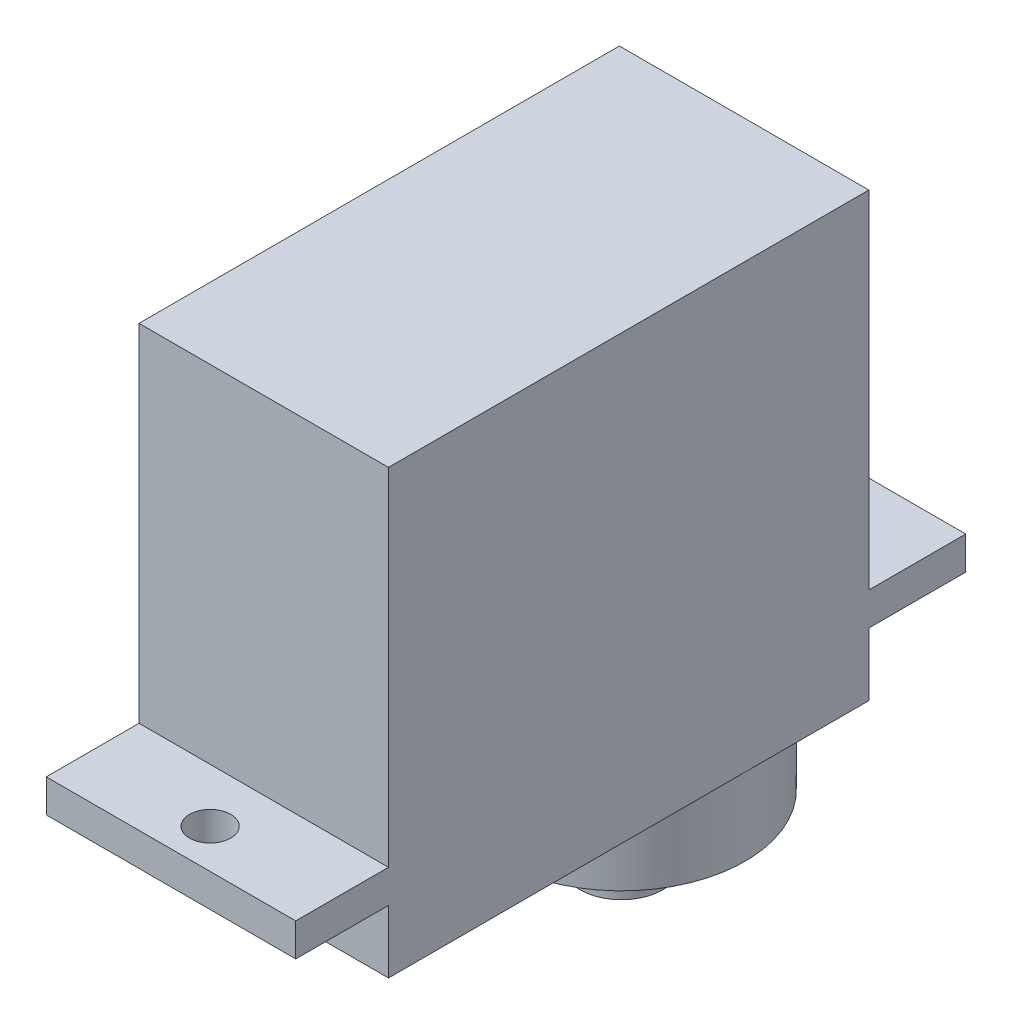
SolidWorks part; units mm, degrees
note: The reader was unsure of these and kept them because the rebuilt part matched: shared geometry of "草图4<2>", "草图6<6>", "草图6<7>".
ref_plane "前视基准面" through (0, 0, 0) normal (0, 0, 1) x (1, 0, 0)
ref_plane "上视基准面" through (0, 0, 0) normal (0, 1, 0) x (1, 0, 0)
ref_plane "右视基准面" through (0, 0, 0) normal (1, 0, 0) x (0, 0, -1)
other "Configuration Table"
other "图形1"
other "图形 (闭合) -1"
sketch "草图3" plane through (0, 0, 0) normal (1, 0, 0) x (0, 0, -1)
  line L1 (-16.8485, -8.5159) -> (15.6515, -8.5159)
  line L2 (-16.8485, -8.5159) -> (-16.8485, 12.9341)
  line L3 (-16.8485, 12.9341) -> (15.6515, 12.9341)
  line L4 (15.6515, -8.5159) -> (15.6515, 12.9341)
  dimension "D1" = 32.5
  dimension "D2" = 21.45
  dimension "D3" = 15.6515
  dimension "D4" = 12.9341
extrude "凸台-拉伸1" add sketch "草图3" along normal mid plane 12.1
sketch "草图4" plane through (0, 0, 0) normal (0, 1, 0) x (1, 0, 0)
  line L0 (0, 0) -> (15.913, 0) construction
  line L1 (-6.05, 10.9515) -> (6.05, 10.9515)
  line L2 (-6.05, 10.9515) -> (-6.05, 15.6516)
  line L3 (-6.05, 15.6516) -> (6.05, 15.6516)
  line L4 (6.05, 10.9515) -> (6.05, 15.6516)
  line L6 (-6.05, -16.9484) -> (6.05, -16.9484)
  line L7 (-6.05, -16.9484) -> (-6.05, -12.3484)
  line L8 (-6.05, -12.3484) -> (6.05, -12.3484)
  line L9 (6.05, -16.9484) -> (6.05, -12.3484)
  dimension "D1" = 12.1
  dimension "D2" = 4.7
  dimension "D3" = 10.9515
  dimension "D4" = 6.05
  dimension "D5" = 4.6
  dimension "D6" = 12.1
  dimension "D7" = 6.05
  dimension "D8" = 12.3484
extrude "切除-拉伸1" cut sketch "草图4" along normal through all from offset 3.8658 offset against normal yes
extrude "切除-拉伸2" cut sketch "草图4<2>" against normal through all from offset 5.4658 offset against normal yes
sketch "草图4<2>" plane through (0, 0, 0) normal (0, 1, 0) x (1, 0, 0) same geometry as "草图4"
sketch "草图5" plane through (0, 0, 0) normal (0, 1, 0) x (1, 0, 0)
  circle A0 centre (0, 13.55) radius 1
  circle A1 centre (0, -14.9492) radius 1
  point P3 (0, 0)
  point P4 (0, -14.951)
  point P6 (0, 0)
  point P9 (0, -14.9166)
  point P10 (0, -14.9492)
  dimension "D1" = 2
  dimension "D2" = 13.55
  dimension "D3" = 2
  dimension "D4" = 14.9492
extrude "切除-拉伸3" cut sketch "草图5" against normal through all
sketch "草图6" plane through (0, 0, 0) normal (0, 1, 0) x (1, 0, 0)
  circle A0 centre (0, 5.0015) radius 6
  circle A1 centre (0, 5.0015) radius 1.25
  circle A2 centre (0, 5.0015) radius 2
extrude "凸台-拉伸2" add sketch "草图6" against normal blind 3.7991 from offset 8.5159 contours A0 A2 | A2 A1 offset against normal yes
extrude "凸台-拉伸3" add sketch "草图6<6>" against normal blind 3.2 from offset 12.3159 contours A2 A1 offset against normal yes
sketch "草图6<6>" plane through (0, 0, 0) normal (0, 1, 0) x (1, 0, 0) same geometry as "草图6"
extrude "切除-拉伸4" cut sketch "草图6<7>" against normal through all contours A1
sketch "草图6<7>" plane through (0, 0, 0) normal (0, 1, 0) x (1, 0, 0) same geometry as "草图6"
